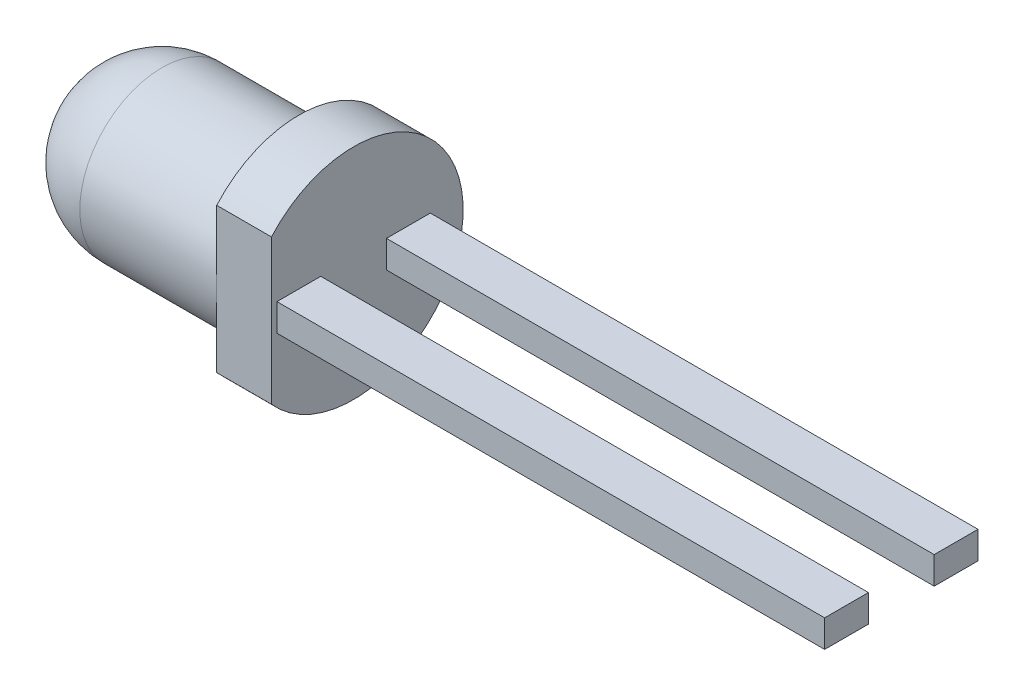
SolidWorks part; units mm, degrees
ref_plane "Спереди" through (0, 0, 0) normal (0, 0, 1) x (1, 0, 0)
ref_plane "Сверху" through (0, 0, 0) normal (0, 1, 0) x (1, 0, 0)
ref_plane "Справа" through (0, 0, 0) normal (1, 0, 0) x (0, 0, -1)
sketch "Эскиз1" plane through (0, 0, 0) normal (0, 0, 1) x (1, 0, 0)
  line L0 (0, 0) -> (-50000, 0) construction
  line L1 (0, 0) -> (0, 2)
  line L2 (0, 2) -> (-1, 2)
  line L3 (-1, 2) -> (-1, 1.5)
  line L4 (-1, 1.5) -> (-3.5, 1.5)
  line L5 (-5, 0) -> (0, 0)
  arc A0 (-3.5, 1.5) -> (-5, 0) centre (-3.5, 0) ccw
  dimension "D1" = 3
  dimension "D2" = 5
  dimension "D3" = 4
  dimension "D4" = 1
revolve "Повернуть1" add sketch "Эскиз1" angle 360 about L0
sketch "Эскиз2" plane through (0, 0, 0) normal (1, 0, 0) x (0, 0, -1)
  line L0 (0, 0) -> (50000, 0) construction
  line L2 (-1.4, 0.25) -> (-0.6, 0.25)
  line L3 (-1.4, 0.25) -> (-1.4, -0.25)
  line L4 (-1.4, -0.25) -> (-0.6, -0.25)
  line L5 (-0.6, 0.25) -> (-0.6, -0.25)
  line L6 (-1.4, 0.25) -> (-0.6, -0.25) construction
  line L7 (-1.4, -0.25) -> (-0.6, 0.25) construction
  line L8 (0.6, 0.25) -> (1.4, 0.25)
  line L9 (0.6, 0.25) -> (0.6, -0.25)
  line L10 (0.6, -0.25) -> (1.4, -0.25)
  line L11 (1.4, 0.25) -> (1.4, -0.25)
  line L12 (0.6, 0.25) -> (1.4, -0.25) construction
  line L13 (0.6, -0.25) -> (1.4, 0.25) construction
  point P3 (-1, 0)
  point P8 (1, 0)
  dimension "D1" = 0.5
  dimension "D2" = 0.8
  dimension "D3" = 1
  dimension "D4" = 1
extrude "Бобышка-Вытянуть1" add sketch "Эскиз2" along normal blind 10 separate body
sketch "Эскиз3" plane through (-1, 0, 0) normal (-1, 0, 0) x (0, 0, 1)
  line L1 (2.5, 1.3229) -> (1.5, 1.3229)
  line L2 (2.5, 1.3229) -> (2.5, -1.3229)
  line L3 (2.5, -1.3229) -> (1.5, -1.3229)
  line L4 (1.5, 1.3229) -> (1.5, -1.3229)
  line L5 (2.5, 1.3229) -> (1.5, -1.3229) construction
  line L6 (2.5, -1.3229) -> (1.5, 1.3229) construction
  circle A0 centre (0, 0) radius 2 construction
  circle A1 centre (0, 0) radius 1.5 construction
  point P0 (2, 0)
extrude "Вырез-Вытянуть1" cut sketch "Эскиз3" against normal through all
